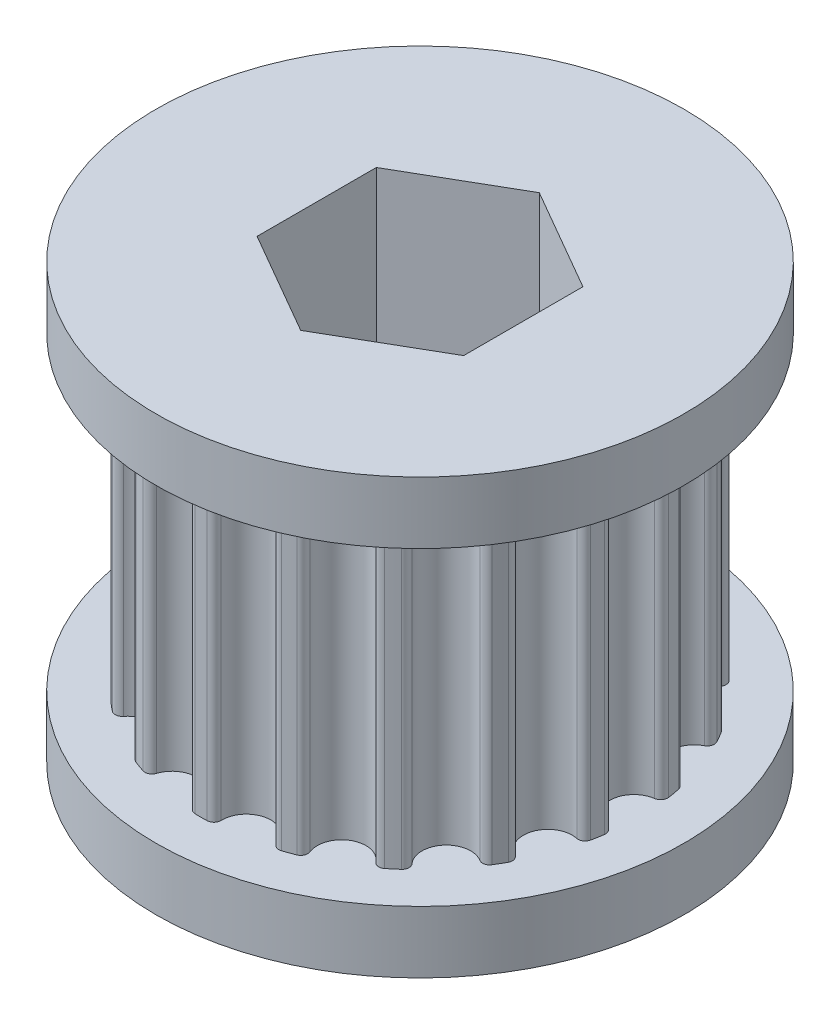
SolidWorks part; units mm, degrees
ref_plane "Front Plane" through (0, 0, 0) normal (0, 0, 1) x (1, 0, 0)
ref_plane "Top Plane" through (0, 0, 0) normal (0, 1, 0) x (1, 0, 0)
ref_plane "Right Plane" through (0, 0, 0) normal (1, 0, 0) x (0, 0, -1)
sketch "mountingHoles" plane through (0, 0, 0) normal (0, 1, 0) x (1, 0, 0)
  line L1 (0, 7.3323) -> (-6.35, 3.6662)
  line L2 (-6.35, 3.6662) -> (-6.35, -3.6662)
  line L3 (-6.35, -3.6662) -> (0, -7.3323)
  line L4 (0, -7.3323) -> (6.35, -3.6662)
  line L5 (6.35, -3.6662) -> (6.35, 3.6662)
  line L6 (6.35, 3.6662) -> (0, 7.3323)
  circle A0 centre (0, 0) radius 14.3239
  circle A16 centre (0, 0) radius 6.35 construction
  point P26 (0, 0)
  point P36 (0, -0.8066)
  dimension "D2" = 12.7
extrude "Boss-Extrude1" add sketch "mountingHoles" along normal mid plane 19.05 contours A0
sketch "Sketch2" plane through (0, 9.525, 0) normal (0, 1, 0) x (1, 0, 0)
  line L0 (0, 0) -> (0, 39.4817) construction
  line L1 (0, 0) -> (2.2844, 12.9557) construction
  line L2 (0, 13.4603) -> (0, 14.3239)
  line L3 (2.2844, 12.9557) -> (6.9027, 39.1471) construction
  line L4 (4.6037, 12.6486) -> (4.8991, 13.4601)
  arc A0 (0, 13.4603) -> (0.367, 13.4553) centre (0, 0) cw
  arc A1 (0.367, 13.4553) -> (0.7868, 13.0085) centre (0.3552, 13.0237) cw
  arc A2 (0.7868, 13.0085) -> (3.7098, 12.4931) centre (2.2844, 12.9557) ccw
  circle A3 centre (0, 0) radius 14.3239 construction
  arc A4 (4.2571, 12.7694) -> (3.7098, 12.4931) centre (4.1206, 12.3598) ccw
  arc A5 (4.6037, 12.6486) -> (4.2571, 12.7694) centre (0, 0) ccw
  arc A6 (0, 14.3239) -> (4.8991, 13.4601) centre (0, 0) cw
  point P13 (2.4873, 14.1063)
  point P14 (2.0242, 11.4799)
  dimension "D3" = 0.8636
  dimension "D4" = 10
  dimension "D2" = 1.4986
  dimension "D1" = 0.4318
  dimension "D5" = 2.667
extrude "Cut-Extrude1" cut sketch "Sketch2" against normal blind 19.05 contours A6 L4 A5 A4 A2 A1 A0 L2
pattern_circular "CirPattern1" count 18 over 360 about axis through (0, 9.525, 0) along (0, -1, 0) of "Cut-Extrude1" reverse direction yes
sketch "flange" plane through (0, 9.525, 0) normal (0, 1, 0) x (1, 0, 0)
  circle A0 centre (0, 0) radius 16.2289
  dimension "D1" = 32.4579
extrude "Boss-Extrude2" add sketch "flange" along normal blind 3.81 contours A0
sketch "Sketch6" plane through (0, -9.525, 0) normal (0, -1, 0) x (1, 0, 0)
  circle A0 centre (0, 0) radius 16.2289
  dimension "D1" = 32.4579
extrude "Boss-Extrude3" add sketch "Sketch6" along normal blind 3.81
extrude "Cut-Extrude5" cut sketch "Sketch1<5>" against normal blind 31.242 and the other way blind 32.512 contours L1 L2 L3 L4 L5 L6
sketch "Sketch1<5>" plane through (0, 0, 0) normal (0, 1, 0) x (1, 0, 0) same geometry as "mountingHoles"
equation "\"n\"= 18"
equation "\"p\"= 5mm"
equation "\"pd\"= \"n\" * \"p\" / 3.1415926"
